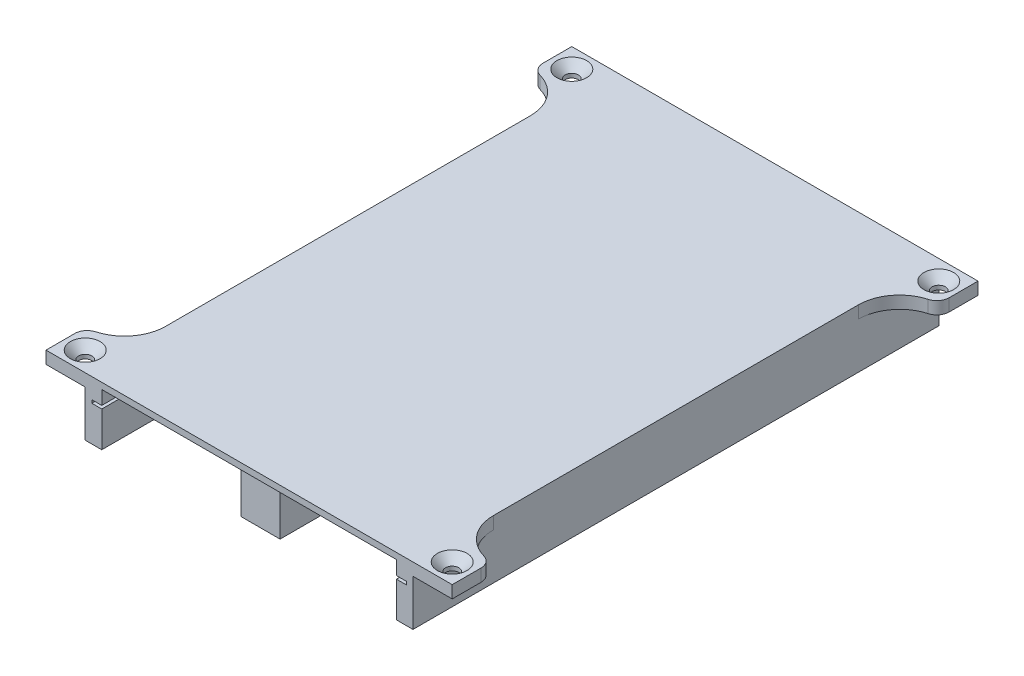
SolidWorks part; units mm, degrees
material "PLA"
ref_plane "Спереди" through (0, 0, 0) normal (0, 0, 1) x (1, 0, 0)
ref_plane "Сверху" through (0, 0, 0) normal (0, 1, 0) x (1, 0, 0)
ref_plane "Справа" through (0, 0, 0) normal (1, 0, 0) x (0, 0, -1)
sketch "Эскиз1" plane through (0, 0, 0) normal (0, 1, 0) x (1, 0, 0)
  line L0 (0, 0) -> (-4740.9496, 0) construction
  line L1 (0, 0) -> (0, -4740.9496) construction
  line L2 (35.675, 63.65) -> (39.675, 63.65)
  line L3 (-35.675, -63.65) -> (-39.675, -63.65)
  line L4 (-35.675, -63.65) -> (-35.675, 63.65)
  line L5 (-35.675, 63.65) -> (-39.675, 63.65)
  line L6 (-39.675, -63.65) -> (-39.675, 63.65)
  line L7 (-35.675, -63.65) -> (-39.675, 63.65) construction
  line L8 (-35.675, 63.65) -> (-39.675, -63.65) construction
  line L9 (39.675, -63.65) -> (39.675, 63.65)
  line L10 (35.675, -63.65) -> (39.675, -63.65)
  line L11 (35.675, -63.65) -> (35.675, 63.65)
  line L12 (35.675, 63.65) -> (39.675, -63.65) construction
  line L13 (35.675, -63.65) -> (39.675, 63.65) construction
  point P5 (-37.675, 0)
  point P14 (37.675, 0)
  dimension "D1" = 4
  dimension "D2" = 127.3
  dimension "D3" = 71.35
extrude "Бобышка-Вытянуть1" add sketch "Эскиз1" along normal blind 12.65
sketch "Эскиз2" plane through (0, 12.65, 0) normal (0, 1, 0) x (1, 0, 0)
  line L1 (39.675, 63.65) -> (-39.675, 63.65)
  line L2 (39.675, 63.65) -> (39.675, -63.65)
  line L3 (39.675, -63.65) -> (-39.675, -63.65)
  line L4 (-39.675, 63.65) -> (-39.675, -63.65)
extrude "Бобышка-Вытянуть2" add sketch "Эскиз2" along normal blind 1.5
sketch "Эскиз3" plane through (0, 0, -63.65) normal (0, 0, -1) x (-1, 0, 0)
  line L0 (0, 0) -> (0, 50000) construction
  line L1 (-35.675, 12.65) -> (-35.675, 0) construction
  line L2 (-35.675, 9.3) -> (-38.075, 9.3)
  line L3 (-35.675, 9.3) -> (-35.675, 8.55)
  line L4 (-35.675, 8.55) -> (-38.075, 8.55)
  line L5 (-38.075, 9.3) -> (-38.075, 8.55)
  line L6 (35.675, 8.55) -> (38.075, 8.55)
  line L7 (38.075, 9.3) -> (38.075, 8.55)
  line L8 (35.675, 9.3) -> (38.075, 9.3)
  line L9 (35.675, 9.3) -> (35.675, 8.55)
  line L10 (-39.675, 0) -> (-35.675, 0) construction
  dimension "D1" = 2.4
  dimension "D2" = 0.75
  dimension "D3" = 8.55
extrude "Вырез-Вытянуть1" cut sketch "Эскиз3" against normal through all from offset 1.5 offset against normal yes
sketch "Эскиз4" plane through (0, 12.65, 0) normal (0, -1, 0) x (1, 0, 0)
  line L0 (35.675, -63.65) -> (35.675, 63.65) construction
  line L1 (-35.675, -63.65) -> (35.675, -63.65)
  line L2 (-35.675, -63.65) -> (-35.675, -62.15)
  line L3 (-35.675, -62.15) -> (35.675, -62.15)
  line L4 (35.675, -63.65) -> (35.675, -62.15)
  dimension "D1" = 1.5
extrude "Бобышка-Вытянуть3" add sketch "Эскиз4" along normal up to surface (12.65 mm away) up to face at (37.675, 0, 0)
sketch "Эскиз5" plane through (0, 14.15, 0) normal (0, 1, 0) x (1, 0, 0)
  line L0 (0, 0) -> (0, 50000) construction
  line L1 (0, 0) -> (-50000, 0) construction
  line L2 (-49.175, 63.65) -> (-39.675, 54.15) construction
  line L3 (-39.675, 63.65) -> (-49.175, 63.65)
  line L4 (-39.675, 63.65) -> (-39.675, 54.15)
  line L5 (-39.675, 54.15) -> (-49.175, 54.15)
  line L6 (-49.175, 63.65) -> (-49.175, 54.15)
  line L7 (-39.675, 63.65) -> (-49.175, 54.15) construction
  line L8 (-39.675, -63.65) -> (-49.175, -54.15) construction
  line L9 (-49.175, -63.65) -> (-39.675, -54.15) construction
  line L10 (-49.175, -63.65) -> (-49.175, -54.15)
  line L11 (-39.675, -54.15) -> (-49.175, -54.15)
  line L12 (-39.675, -63.65) -> (-39.675, -54.15)
  line L13 (-39.675, -63.65) -> (-49.175, -63.65)
  line L14 (49.175, -63.65) -> (39.675, -54.15) construction
  line L15 (39.675, -63.65) -> (49.175, -54.15) construction
  line L16 (39.675, 63.65) -> (49.175, 54.15) construction
  line L17 (49.175, 63.65) -> (39.675, 54.15) construction
  line L18 (39.675, -63.65) -> (49.175, -63.65)
  line L19 (39.675, -63.65) -> (39.675, -54.15)
  line L20 (39.675, -54.15) -> (49.175, -54.15)
  line L21 (49.175, -63.65) -> (49.175, -54.15)
  line L22 (49.175, 63.65) -> (49.175, 54.15)
  line L23 (39.675, 54.15) -> (49.175, 54.15)
  line L24 (39.675, 63.65) -> (39.675, 54.15)
  line L25 (39.675, 63.65) -> (49.175, 63.65)
  circle A0 centre (-44.425, 58.9) radius 1.6
  circle A1 centre (-44.425, 58.9) radius 2.75 construction
  circle A2 centre (-44.425, -58.9) radius 2.75 construction
  circle A3 centre (-44.425, -58.9) radius 1.6
  circle A4 centre (44.425, -58.9) radius 2.75 construction
  circle A5 centre (44.425, 58.9) radius 2.75 construction
  circle A6 centre (44.425, -58.9) radius 1.6
  circle A7 centre (44.425, 58.9) radius 1.6
  dimension "D1" = 3.2
  dimension "D2" = 5.5
  dimension "D3" = 9.5
extrude "Бобышка-Вытянуть4" add sketch "Эскиз5" against normal blind 3
chamfer "Фаска1" distance 2 angle 45 4 edges at (44.425, 14.15, 60.5) (-44.425, 14.15, 57.3) (44.425, 14.15, -60.5) (-44.425, 14.15, -57.3)
fillet "Скругление1" radius 10 4 edges at (39.675, 12.65, 54.15) (39.675, 12.65, -54.15) (-39.675, 12.65, 54.15) (-39.675, 12.65, -54.15)
fillet "Скругление2" radius 3 4 edges at (-49.175, 12.65, 54.15) (49.175, 12.65, 54.15) (49.175, 12.65, -54.15) (-49.175, 12.65, -54.15)
sketch "Эскиз6" plane through (0, 12.65, 0) normal (0, -1, 0) x (1, 0, 0)
  line L0 (35.675, -62.15) -> (35.675, 63.65) construction
  line L1 (32.325, -52.35) -> (24.825, -52.35)
  line L2 (32.325, -52.35) -> (32.325, -62.15)
  line L3 (32.325, -59.85) -> (24.825, -59.85) construction
  line L4 (24.825, -52.35) -> (24.825, -62.15)
  line L5 (32.325, -52.35) -> (24.825, -59.85) construction
  line L6 (32.325, -59.85) -> (24.825, -52.35) construction
  line L7 (35.675, -62.15) -> (-35.675, -62.15) construction
  line L8 (32.325, -62.15) -> (24.825, -62.15)
  circle A0 centre (28.575, -56.1) radius 2.1 construction
  point P0 (28.575, -56.1)
  dimension "D3" = 4.2
  dimension "D4" = 1.65
  dimension "D5" = 1.65
  dimension "D1" = 7.1
  dimension "D2" = 6.05
extrude "Бобышка-Вытянуть5" add sketch "Эскиз6" along normal blind 9.6
sketch "Эскиз7" plane through (0, 3.05, 0) normal (0, -1, 0) x (1, 0, 0)
  line L0 (24.825, -52.35) -> (32.325, -59.85) construction
  line L1 (32.325, -52.35) -> (24.825, -59.85) construction
  line L2 (32.325, -62.15) -> (32.325, -52.35) construction
  line L3 (24.825, -52.35) -> (24.825, -62.15) construction
  circle A0 centre (28.575, -56.1) radius 2.05
  dimension "D1" = 4.1
extrude "Вырез-Вытянуть2" cut sketch "Эскиз7" against normal blind 4.5
sketch "Эскиз8" plane through (0, 0, 0) normal (0, -1, 0) x (1, 0, 0)
  line L0 (-35.675, 63.65) -> (-35.675, -62.15) construction
  line L1 (-35.675, 38.05) -> (-38.075, 38.05)
  line L2 (-35.675, 38.05) -> (-35.675, 32.2)
  line L3 (-35.675, 32.2) -> (-38.075, 32.2)
  line L4 (-38.075, 38.05) -> (-38.075, 32.2)
  line L5 (0, 0) -> (0, 50000) construction
  line L6 (-35.675, -16.55) -> (-38.075, -16.55)
  line L7 (-35.675, -16.55) -> (-35.675, -22.4)
  line L8 (-35.675, -22.4) -> (-38.075, -22.4)
  line L9 (-38.075, -16.55) -> (-38.075, -22.4)
  line L10 (-39.675, 63.65) -> (-35.675, 63.65) construction
  line L11 (35.675, -22.4) -> (38.075, -22.4)
  line L12 (38.075, -16.55) -> (38.075, -22.4)
  line L13 (35.675, -16.55) -> (38.075, -16.55)
  line L14 (35.675, -16.55) -> (35.675, -22.4)
  line L15 (35.675, 32.2) -> (38.075, 32.2)
  line L16 (38.075, 38.05) -> (38.075, 32.2)
  line L17 (35.675, 38.05) -> (38.075, 38.05)
  line L18 (35.675, 38.05) -> (35.675, 32.2)
  line L19 (39.675, -63.65) -> (-39.675, -63.65) construction
  point P26 (0, -63.65)
  dimension "D1" = 2.4
  dimension "D2" = 5.85
  dimension "D3" = 48.75
  dimension "D4" = 25.6
extrude "Вырез-Вытянуть3" cut sketch "Эскиз8" against normal up to surface (8.55 mm away) up to face at (-36.875, 8.55, 0.75)
sketch "Эскиз10" plane through (0, 12.65, 0) normal (0, -1, 0) x (1, 0, 0)
  line L0 (-35.675, 63.65) -> (-35.675, -62.15) construction
  line L1 (-25.275, -51.75) -> (-28.275, -51.75)
  line L2 (-25.275, -51.75) -> (-25.275, -57.7)
  line L3 (-25.275, -57.7) -> (-28.275, -57.7)
  line L4 (-28.275, -51.75) -> (-28.275, -57.7)
  line L5 (24.825, -62.15) -> (-35.675, -62.15) construction
  line L6 (35.675, -62.15) -> (-35.675, -62.15) construction
  line L8 (15.225, -51.75) -> (18.225, -51.75)
  line L9 (15.225, -51.75) -> (15.225, -57.7)
  line L10 (15.225, -57.7) -> (18.225, -57.7)
  line L11 (18.225, -51.75) -> (18.225, -57.7)
  dimension "D1" = 10.4
  dimension "D2" = 4.45
  dimension "D3" = 10.4
  dimension "D4" = 3
  dimension "D5" = 50.9
extrude "Бобышка-Вытянуть6" add sketch "Эскиз10" along normal blind 3.95
sketch "Эскиз11" plane through (0, 12.65, 0) normal (0, -1, 0) x (1, 0, 0)
  line L1 (-25.275, -57.7) -> (15.225, -57.7)
  line L2 (-25.275, -57.7) -> (-25.275, -51.75)
  line L3 (-25.275, -51.75) -> (15.225, -51.75)
  line L4 (15.225, -57.7) -> (15.225, -51.75)
extrude "Бобышка-Вытянуть7" add sketch "Эскиз11" along normal blind 0.35
fillet "Скругление4" radius 4 1 edges at (-5.025, 12.65, -57.7)
fillet "Скругление5" radius 2 2 edges at (-26.775, 8.7, -57.7) (16.725, 8.7, -57.7)
sketch "Эскиз12" plane through (0, 0, -62.15) normal (0, 0, 1) x (1, 0, 0)
  line L0 (24.825, 12.65) -> (-35.675, 12.65) construction
  line L1 (15.475, 8) -> (-25.525, 8)
  line L2 (15.475, 8) -> (15.475, 12.65)
  line L12 (15.475, 12.65) -> (-25.525, 12.65)
  line L13 (-25.525, 8) -> (-25.525, 12.65)
  line L15 (-5.025, 12.3) -> (-5.025, 12.65) construction
  line L17 (-25.275, 12.3) -> (15.225, 12.3) construction
  point P13 (-5.025, 12.3)
  dimension "D1" = 4.65
  dimension "D2" = 41
extrude "Вырез-Вытянуть4" cut sketch "Эскиз12" against normal through all
sketch "Эскиз13" plane through (0, 12.65, 0) normal (0, -1, 0) x (1, 0, 0)
  line L0 (0, 63.65) -> (0, 50063.65) construction
  line L1 (-35.675, 63.65) -> (35.675, 63.65) construction
  line L3 (4.75, 60.9) -> (-4.75, 60.9)
  line L4 (4.75, 60.9) -> (4.75, 51.4)
  line L5 (4.75, 51.4) -> (-4.75, 51.4)
  line L6 (-4.75, 60.9) -> (-4.75, 51.4)
  line L7 (4.75, 60.9) -> (-4.75, 51.4) construction
  line L8 (4.75, 51.4) -> (-4.75, 60.9) construction
  circle A0 centre (0, 56.15) radius 2.75 construction
  point P4 (0, 63.65)
  point P5 (0, 56.15)
  dimension "D1" = 5.5
  dimension "D2" = 2
  dimension "D3" = 7.5
extrude "Бобышка-Вытянуть8" add sketch "Эскиз13" along normal blind 12.55
sketch "Эскиз14" plane through (0, 0.1, 0) normal (0, -1, 0) x (1, 0, 0)
  line L0 (-4.75, 60.9) -> (4.75, 51.4) construction
  line L1 (4.75, 60.9) -> (-4.75, 51.4) construction
  circle A0 centre (0, 56.15) radius 1.6
  dimension "D1" = 3.2
extrude "Вырез-Вытянуть5" cut sketch "Эскиз14" against normal blind 7
